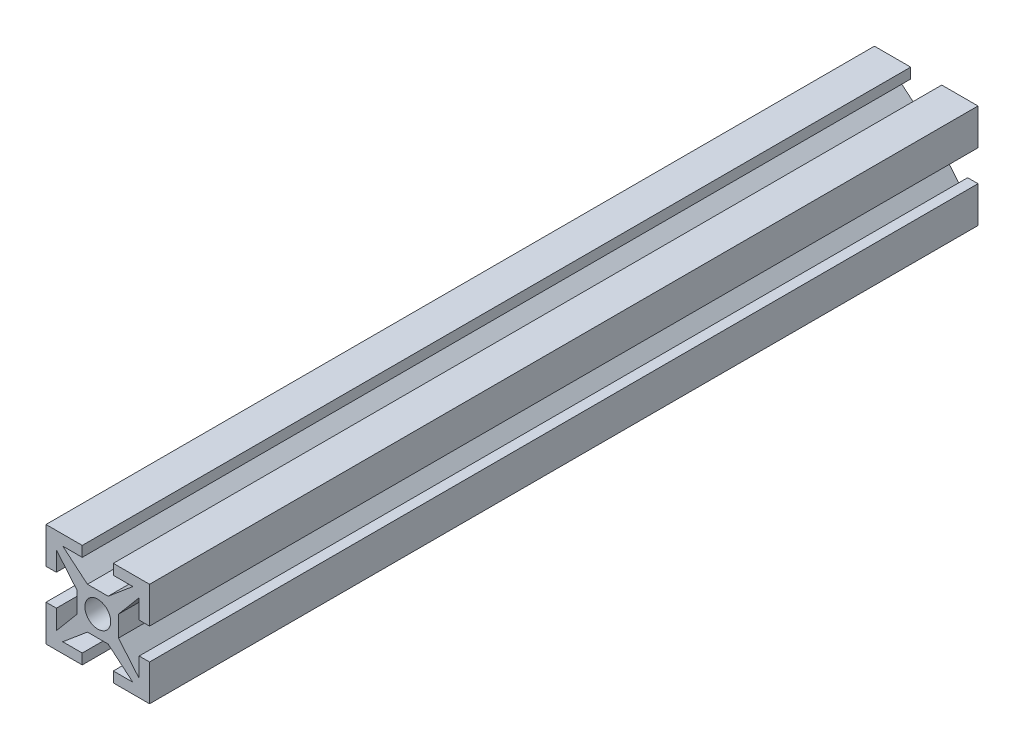
SolidWorks part; units mm, degrees
ref_plane "Front Plane" through (0, 0, 0) normal (0, 0, 1) x (1, 0, 0)
ref_plane "Top Plane" through (0, 0, 0) normal (0, 1, 0) x (1, 0, 0)
ref_plane "Right Plane" through (0, 0, 0) normal (1, 0, 0) x (0, 0, -1)
sketch "Esquisse2" plane through (0, 0, 0) normal (0, 0, 1) x (1, 0, 0)
  line L0 (-1, -2) -> (1, -2)
  line L1 (1, -2) -> (3.3835, -4)
  line L2 (3.3835, -4) -> (1.5, -4)
  line L3 (1.5, -4) -> (1.5, -5)
  line L4 (1.5, -5) -> (5, -5)
  line L5 (-1, -2) -> (-3.3835, -4)
  line L6 (-3.3835, -4) -> (-1.5, -4)
  line L7 (-1.5, -4) -> (-1.5, -5)
  line L8 (-1.5, -5) -> (-5, -5)
  line L9 (-5, -5) -> (-5, -1.5)
  line L10 (-5, -1.5) -> (-4, -1.5)
  line L11 (-4, -1.5) -> (-4, -3.3835)
  line L12 (-4, -3.3835) -> (-2, -1)
  line L13 (-2, -1) -> (-2, 1)
  line L14 (-2, 1) -> (-4, 3.3835)
  line L15 (-4, 3.3835) -> (-4, 1.5)
  line L16 (-4, 1.5) -> (-5, 1.5)
  line L17 (-5, 1.5) -> (-5, 5)
  line L18 (-5, 5) -> (-1.5, 5)
  line L19 (-1.5, 5) -> (-1.5, 4)
  line L20 (-1.5, 4) -> (-3.3835, 4)
  line L21 (-3.3835, 4) -> (-1, 2)
  line L22 (-1, 2) -> (1, 2)
  line L23 (1, 2) -> (3.3835, 4)
  line L24 (3.3835, 4) -> (1.5, 4)
  line L25 (1.5, 4) -> (1.5, 5)
  line L26 (1.5, 5) -> (5, 5)
  line L27 (5, 5) -> (5, 1.5)
  line L28 (5, 1.5) -> (4, 1.5)
  line L29 (4, 1.5) -> (4, 3.3835)
  line L30 (4, 3.3835) -> (2, 1)
  line L31 (2, -1) -> (2, 1)
  line L32 (2, -1) -> (4, -3.3835)
  line L33 (4, -3.3835) -> (4, -1.5)
  line L34 (4, -1.5) -> (5, -1.5)
  line L35 (5, -1.5) -> (5, -5)
  circle A0 centre (0, 0) radius 1.25
  point P4 (0, -2)
  point P34 (0, 2)
  point P40 (2, 0)
  dimension "D4" = 2.5
  dimension "D1" = 2
  dimension "D2" = 3.5
  dimension "D3" = 1
  dimension "D5" = 10
  dimension "D6" = 10
  dimension "D7" = 140
  dimension "D8" = 4
  dimension "D9" = 4
  dimension "D10" = 3.5
  dimension "D11" = 3
extrude "Main Extrusion" add sketch "Esquisse2" along normal blind 80
